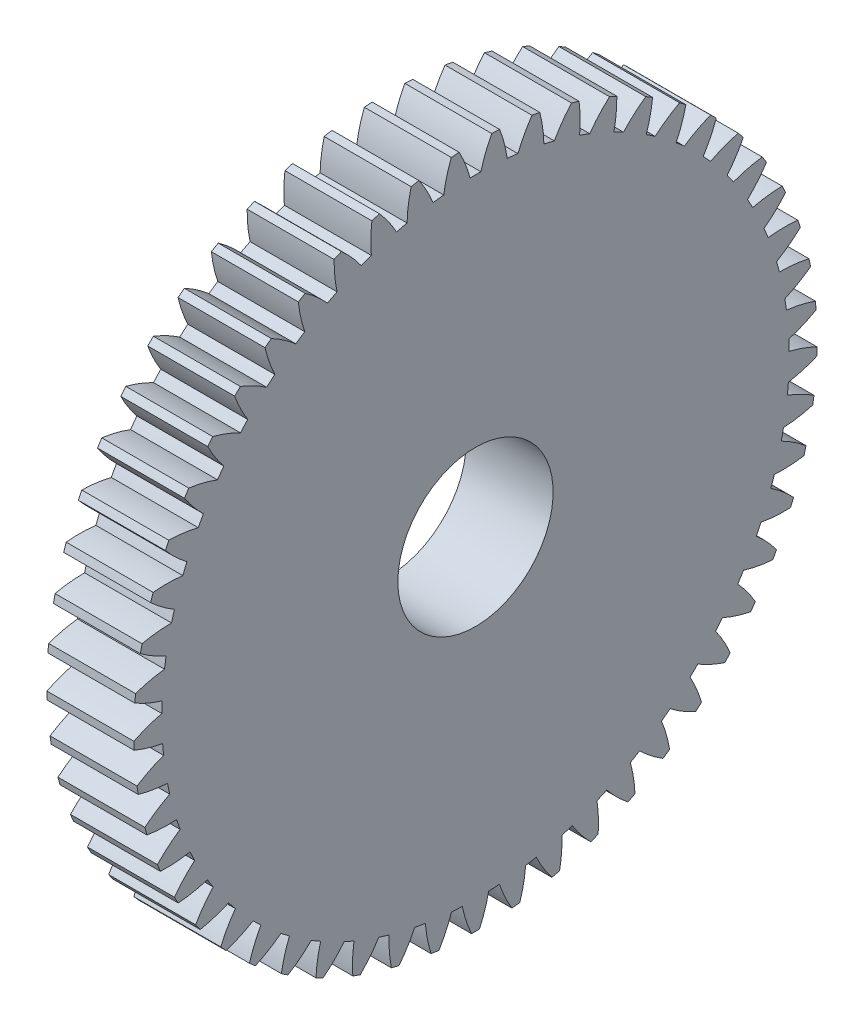
SolidWorks part; units mm, degrees
ref_plane "Plane1" through (0, 0, 0) normal (0, 0, 1) x (1, 0, 0)
ref_plane "Plane2" through (0, 0, 0) normal (0, 1, 0) x (1, 0, 0)
ref_plane "Plane3" through (0, 0, 0) normal (1, 0, 0) x (0, 0, -1)
sketch "HoldingSke" plane through (0, 0, 0) normal (0, 1, 0) x (1, 0, 0)
  line L0 (0, 0) -> (1.5045, -1.9966)
  line L1 (-15, 0) -> (100, 0) construction
  line L2 (0, 0) -> (-2.1039, 2.3779)
  line L3 (0, 0) -> (-11.863, 4.5341)
  line L4 (0, 0) -> (5.1973, 6.897)
  line L5 (0, 0) -> (-46.8476, -17.4728)
  line L6 (0, 0) -> (-2.3211, -1.5661)
  line L7 (-2.1039, 2.3779) -> (8.6586, 51.2059)
  line L8 (-76.2, 54.61) -> (-75.3, 54.61)
  line L9 (-71.009, 38.7566) -> (-53.1078, 45.2721)
  line L10 (-76.2, 71.12) -> (104.1128, 71.12)
  line L11 (0, 0) -> (-2.8, 0)
  line L12 (-76.2, 101.6) -> (-76.185, 101.6)
  line L13 (24.9733, 27.94) -> (52.9518, 28.4284)
  line L14 (24.9733, 27.94) -> (24.9743, 27.94)
  line L15 (24.9733, 27.94) -> (100.4006, 29.5858)
  line L16 (-63.627, -0.4) -> (-12.827, -0.4)
  circle A0 centre (0, 0) radius 2.5
  circle A1 centre (0, 0) radius 10.099
  circle A2 centre (0, 0) radius 37.5
  circle A3 centre (0, 0) radius 2.5
  dimension "Pitch_radius" = 180.3128
sketch "BasProSke" plane through (0, 0, 0) normal (0, 1, 0) x (1, 0, 0)
  line L0 (-10, 0) -> (60, 0) construction
  line L1 (0, 0) -> (0, 11)
  line L2 (0, 0) -> (2.8, 0)
  line L3 (2.8, 0) -> (2.8, 11)
  line L4 (2.8, 11) -> (0, 11)
revolve "Base-Revolve" add sketch "BasProSke" angle 360 about L0
sketch "TooCutSke" plane through (0, 0, 0) normal (1, 0, 0) x (0, 0, -1)
  line L1 (0, 0) -> (0, 107) construction
  line L2 (0, 0) -> (-0.3404, 10.5945) construction
  line L3 (0, 0) -> (-1.2554, 21.155) construction
  line L4 (-0.3404, 10.5945) -> (-0.6277, 10.5775) construction
  arc A0 (0.1736, 10.0975) -> (-0.1736, 10.0975) centre (0, 0) ccw
  arc A1 (0.5371, 11.0123) -> (-0.5371, 11.0123) centre (0, 0) ccw
  circle A2 centre (0, 0) radius 10.6 construction
  circle A3 centre (0, 0) radius 9.9607 construction
  arc A4 (-0.1736, 10.0975) -> (-0.5371, 11.0123) centre (-4.2689, 8.9996) ccw
  arc A5 (0.5371, 11.0123) -> (0.1736, 10.0975) centre (4.2689, 8.9996) ccw
extrude "ToothCut" cut sketch "TooCutSke" along normal through all
fillet "Breaks" [suppressed] radius 0.008 tangent propagation no
fillet "RootFillets" [suppressed] radius 0.101
pattern_circular "TeethCuts" count 53 every 6.792 about axis through (-10, 0, 0) along (1, 0, 0) of "ToothCut", "RootFillets", "Breaks"
sketch "HubNeaOneSke" plane through (0, 0, 0) normal (-1, 0, 0) x (0, 0, 1)
  circle A0 centre (0, 0) radius 10.099
extrude "HubNearOne" [suppressed] add sketch "HubNeaOneSke" along normal blind 47.2001
sketch "HubNeaBotSke" plane through (0, 0, 0) normal (-1, 0, 0) x (0, 0, 1)
  circle A0 centre (0, 0) radius 10.099
extrude "HubNearBoth" [suppressed] add sketch "HubNeaBotSke" along normal blind 23.6
ref_plane "FarPln" through (2.8, 0, 0) normal (1, 0, 0) x (0, 0, -1)
sketch "HubFarSke" plane through (2.8, 0, 0) normal (1, 0, 0) x (0, 0, -1)
  circle A0 centre (0, 0) radius 10.099
extrude "HubFar" [suppressed] add sketch "HubFarSke" along normal blind 23.6
sketch "BorSke" plane through (0, 0, 0) normal (1, 0, 0) x (0, 0, -1)
  circle A0 centre (0, 0) radius 2.5
extrude "Bore" cut sketch "BorSke" along normal mid plane 100.0001
sketch "KeySke" plane through (0, 0, 0) normal (1, 0, 0) x (0, 0, -1)
  line L0 (-1, 0) -> (-1, 3.4)
  line L1 (-1, 3.4) -> (1, 3.4)
  line L2 (1, 3.4) -> (1, 0)
  line L3 (0, 0) -> (0, 34) construction
  line L4 (-1, 0) -> (1, 0)
extrude "Keyway" [suppressed] cut sketch "KeySke" along normal mid plane 100.0001
pattern_circular "Keyway2" [suppressed] count 2 every 90 about axis through (-10, 0, 0) along (1, 0, 0)
equation "' \"Module@HoldingSke\" = 6.35"
equation "' \"Num_teeth@HoldingSke\" = 12"
equation "' \"Ap@HoldingSke\" =  20"
equation "' \"Ap@HoldingSke\" = 20"
equation "' \"Width@HoldingSke\" = 0.5 * 25.4"
equation "' \"Hub_dia@HoldingSke\"= 1 * 25.4"
equation "' \"Hub_dia@HoldingSke\" = 1 * 25.4"
equation "' \"Overall_len@HoldingSke\" = 1.0 * 25.4"
equation "' \"Bore@HoldingSke\" = 0.75 * 25.4"
equation "' \"T_dim@HoldingSke\" = 0.1 * 25.4"
equation "' \"Width@KeySke\" = 0.25 * 25.4"
equation "' \"Show_teeth@HoldingSke\" = 13"
equation "' \"Backlash@HoldingSke\" = 0.009 * 25.4"
equation "' \"Addendum_fac@HoldingSke\" = 1.0"
equation "' \"Dedendum_fac@HoldingSke\" = 1.25"
equation "' \"Dedendum_add@HoldingSke\" = 0.00005 * 25.4"
equation "' \"Clearance_fac@HoldingSke\" = 0.25"
equation "\"Pitch@HoldingSke\" = 1 / \"Module@HoldingSke\""
equation "\"Overcut_dia@TooCutSke\" = (\"Num_teeth@HoldingSke\" + 2 * \"Addendum_fac@HoldingSke\") / \"Pitch@HoldingSke\" + 0.002 * 25.4"
equation "\"Pitch_dia@TooCutSke\" = \"Num_teeth@HoldingSke\" / \"Pitch@HoldingSke\""
equation "\"Base_dia@TooCutSke\" = \"Num_teeth@HoldingSke\" / \"Pitch@HoldingSke\" * cos((\"Ap@HoldingSke\"  * 3.14159265 / 180))"
equation "\"Root_dia@TooCutSke\" = (\"Num_teeth@HoldingSke\" + 2) / \"Pitch@HoldingSke\" - 2 * (\"Addendum_fac@HoldingSke\" + \"Dedendum_fac@HoldingSke\") / \"Pitch@HoldingSke\" - \"Dedendum_add@HoldingSke\" * 2"
equation "\"Half_ang@TooCutSke\" = 180 / \"Num_teeth@HoldingSke\""
equation "\"Half_CT@TooCutSke\" = \"Num_teeth@HoldingSke\" / \"Pitch@HoldingSke\" * sin((3.14159265 / 2 / \"Num_teeth@HoldingSke\")) / 2 - 7 * \"Backlash@HoldingSke\" / 4"
equation "\"Flank_rad@TooCutSke\" = \"Num_teeth@HoldingSke\" / \"Pitch@HoldingSke\" / 5"
equation "\"Radius@RootFillets\" = \"Clearance_fac@HoldingSke\" / \"Pitch@HoldingSke\" + \"Dedendum_add@HoldingSke\""
equation "\"Break_rad@Breaks\" = 0.02 / \"Pitch@HoldingSke\""
equation "\"Thickness@HoldingSke\" = \"Width@HoldingSke\""
equation "\"OAL@HoldingSke\" = \"Thickness@HoldingSke\""
equation "\"MHD@HoldingSke\" = (\"Num_teeth@HoldingSke\" + 2) / \"Pitch@HoldingSke\" - 2 * (\"Addendum_fac@HoldingSke\" + \"Dedendum_fac@HoldingSke\")  / \"Pitch@HoldingSke\" - \"Dedendum_add@HoldingSke\" * 2"
equation "\"MBD@HoldingSke\" = (\"Num_teeth@HoldingSke\" + 2) / \"Pitch@HoldingSke\" - 2 * (\"Addendum_fac@HoldingSke\" + \"Dedendum_fac@HoldingSke\")  / \"Pitch@HoldingSke\" - \"Dedendum_add@HoldingSke\" * 2 - 0.002 * 25.4"
equation "\"MHD@HoldingSke\" = ((sgn( \"MHD@HoldingSke\" - \"Hub_dia@HoldingSke\" )-1)*( \"MHD@HoldingSke\" - \"Hub_dia@HoldingSke\" ))/-2+ \"Hub_dia@HoldingSke\""
equation "\"MBD@HoldingSke\" = ((sgn( \"MBD@HoldingSke\" - \"Bore@HoldingSke\" )-1)*( \"MBD@HoldingSke\" - \"Bore@HoldingSke\" ))/-2+ \"Bore@HoldingSke\""
equation "\"OAL@HoldingSke\" = ((sgn( \"OAL@HoldingSke\" - \"Overall_len@HoldingSke\" )+1)*( \"OAL@HoldingSke\" - \"Overall_len@HoldingSke\" ))/2 + \"Overall_len@HoldingSke\" + 0.000002 * 25.4"
equation "\"Num_teeth@TeethCuts\" = int( \"Show_teeth@HoldingSke\" ) + 1"
equation "\"Num_teeth@TeethCuts\" = ((sgn( \"Num_teeth@TeethCuts\" - \"Num_teeth@HoldingSke\" )-1)*( \"Num_teeth@TeethCuts\" - \"Num_teeth@HoldingSke\" ))/-2+ \"Num_teeth@HoldingSke\""
equation "\"Num_teeth@TeethCuts\" = ((sgn( \"Num_teeth@TeethCuts\" - 2.0)+1)*( \"Num_teeth@TeethCuts\" - 2.0))/2 +2.0"
equation "\"Angle@TeethCuts\" = 360.0 / \"Num_teeth@HoldingSke\""
equation "\"Diameter@BasProSke\" = (\"Num_teeth@HoldingSke\" + 2 * \"Addendum_fac@HoldingSke\") / \"Pitch@HoldingSke\""
equation "\"Thickness@BasProSke\"  = \"Thickness@HoldingSke\""
equation "' \"Fillet_rad@BasProSke\" =  \"Thickness@HoldingSke\" * 0.05"
equation "' \"Fillet_rad@BasProSke\" = \"Thickness@HoldingSke\" * 0.05"
equation "\"MHD@HoldingSke\" = ((sgn( \"MHD@HoldingSke\" - \"Root_dia@TooCutSke\" )-1)*( \"MHD@HoldingSke\" - \"Root_dia@TooCutSke\" ))/-2+ \"Root_dia@TooCutSke\""
equation "\"Diameter@HubNeaOneSke\" = \"MHD@HoldingSke\""
equation "\"Length@HubNearOne\" = \"OAL@HoldingSke\" - \"Thickness@BasProSke\""
equation "\"Diameter@HubNeaBotSke\" = \"MHD@HoldingSke\""
equation "\"Length@HubNearBoth\" = ( \"OAL@HoldingSke\" - \"Thickness@BasProSke\" ) / 2.0"
equation "\"Thickness@FarPln\" = \"Thickness@BasProSke\""
equation "\"Diameter@HubFarSke\" = \"MHD@HoldingSke\""
equation "\"Length@HubFar\" = ( \"OAL@HoldingSke\" - \"Thickness@BasProSke\" ) / 2.0"
equation "\"Diameter@BorSke\" = \"MBD@HoldingSke\""
equation "\"D1@Bore\" = \"OAL@HoldingSke\" * 2.0"
equation "\"D1@Keyway\" = \"OAL@HoldingSke\" * 2.0"
equation "\"Offset@KeySke\" = \"T_dim@HoldingSke\" + \"MBD@HoldingSke\" / 2.0"
